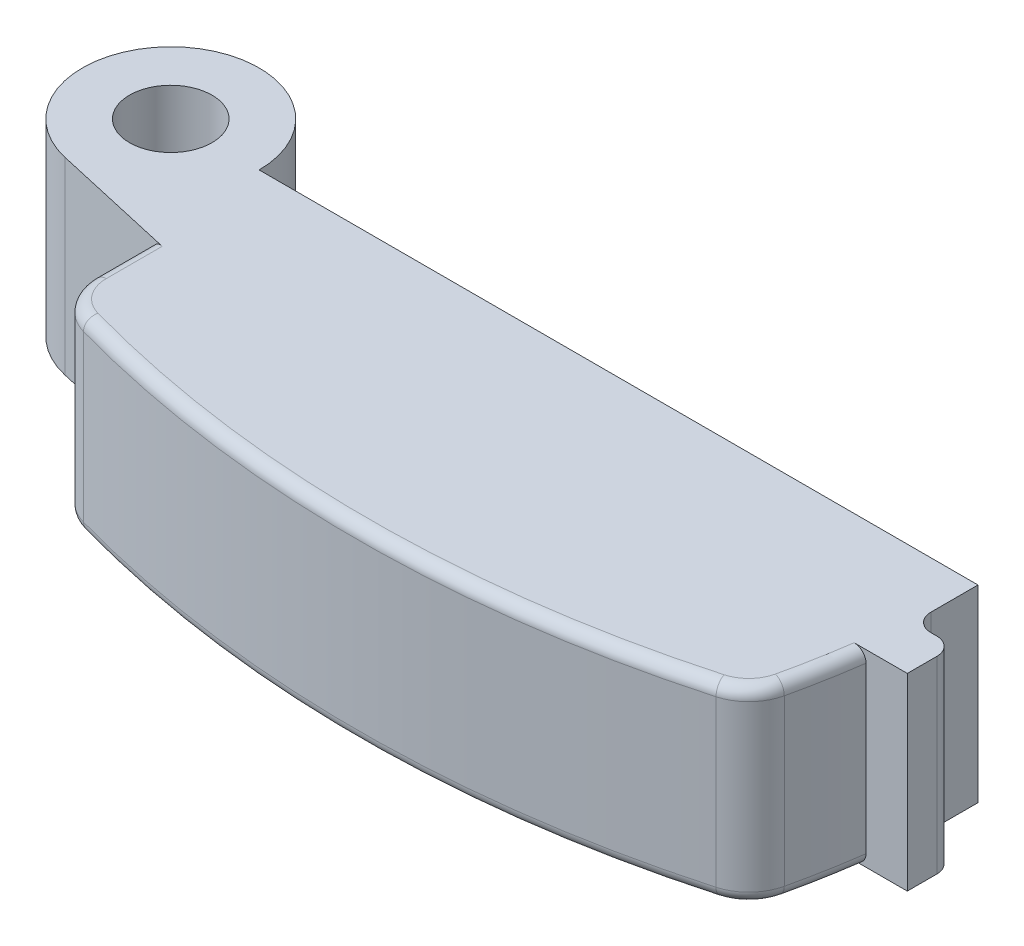
SolidWorks part; units mm, degrees
ref_plane "Front Plane" through (0, 0, 0) normal (0, 0, 1) x (1, 0, 0)
ref_plane "Top Plane" through (0, 0, 0) normal (0, 1, 0) x (1, 0, 0)
ref_plane "Right Plane" through (0, 0, 0) normal (1, 0, 0) x (0, 0, -1)
sketch "Sketch1" plane through (0, 0, 0) normal (0, 1, 0) x (1, 0, 0)
  line L0 (3.75, 0) -> (34.25, 0)
  line L2 (4, -7.2392) -> (4, -4.75)
  line L3 (-0.8277, -3.6575) -> (4, -4.75)
  line L4 (5.3249, -11) -> (19.1895, -11) construction
  line L5 (5.4633, -9.1658) -> (32.3, -9.1658) construction
  line L7 (34.25, 0) -> (34.25, -4.75)
  arc A1 (33.7133, -7.6836) -> (32.3, -9.1658) centre (31.7633, -7.2392) cw
  circle A2 centre (0, 0) radius 1.75
  arc A3 (3.75, 0) -> (-0.8277, -3.6575) centre (0, 0) ccw
  arc A5 (4, -7.2392) -> (5.4633, -9.1658) centre (6, -7.2392) ccw
  arc A6 (5.4633, -9.1658) -> (32.3, -9.1658) centre (18.8817, 39) ccw
  arc A7 (34.25, -4.75) -> (33.7133, -7.6836) centre (0, 0) cw
  dimension "D1" = 34.25
  dimension "D3" = 2
  dimension "D2" = 3.5
  dimension "D4" = 2
  dimension "D6" = 50
  dimension "D5" = 11
  dimension "D7" = 4
  dimension "D8" = 4.75
extrude "Boss-Extrude1" add sketch "Sketch1" against normal mid plane 8
ref_plane "Plane1" through (0, 0, 4.75) normal (0, 0, 1) x (1, 0, 0)
sketch "Sketch3" plane through (0, 0, 4.75) normal (0, 0, -1) x (-1, 0, 0)
  line L5 (-34.25, -4) -> (-34.25, 4) construction
  line L6 (-34.25, -4) -> (-36, -4)
  line L7 (-36, -4) -> (-36, 4)
  line L8 (-36, 4) -> (-34.25, 4)
  line L11 (-34.25, 4) -> (-34.25, -4)
  dimension "D1" = 1.75
extrude "Boss-Extrude2" add sketch "Sketch3" along normal blind 2 contours L6 L7 L8 L11
fillet "Fillet1" radius 0.5 10 edges at (4, 4, 5.9946) (4.4073, 4, 8.4488) (34.0133, 4, 6.2226) (33.2108, 4, 8.6193) (4, -4, 5.9946) (4.4073, -4, 8.4488) (34.0133, -4, 6.2226) (33.2108, -4, 8.6193) (18.8817, 4, 11) (18.8817, -4, 11)
sketch "Sketch4" plane through (0, 0, 0) normal (0, 0, -1) x (-1, 0, 0)
  line L0 (-30, 0) -> (0, 0) construction
  line L1 (-32, 2.5) -> (-28, 2.5)
  line L2 (-32, 2.5) -> (-32, -2.5)
  line L3 (-32, -2.5) -> (-28, -2.5)
  line L4 (-28, 2.5) -> (-28, -2.5)
  line L5 (-32, 2.5) -> (-28, -2.5) construction
  line L6 (-32, -2.5) -> (-28, 2.5) construction
  point P0 (-30, 0)
  dimension "D1" = 4
  dimension "D2" = 5
  dimension "D3" = 30
extrude "Cut-Extrude1" cut sketch "Sketch4" against normal blind 4
fillet "Fillet2" radius 0.75 2 edges at (36, 0, 2.75) (34.25, 0, 2.75)
